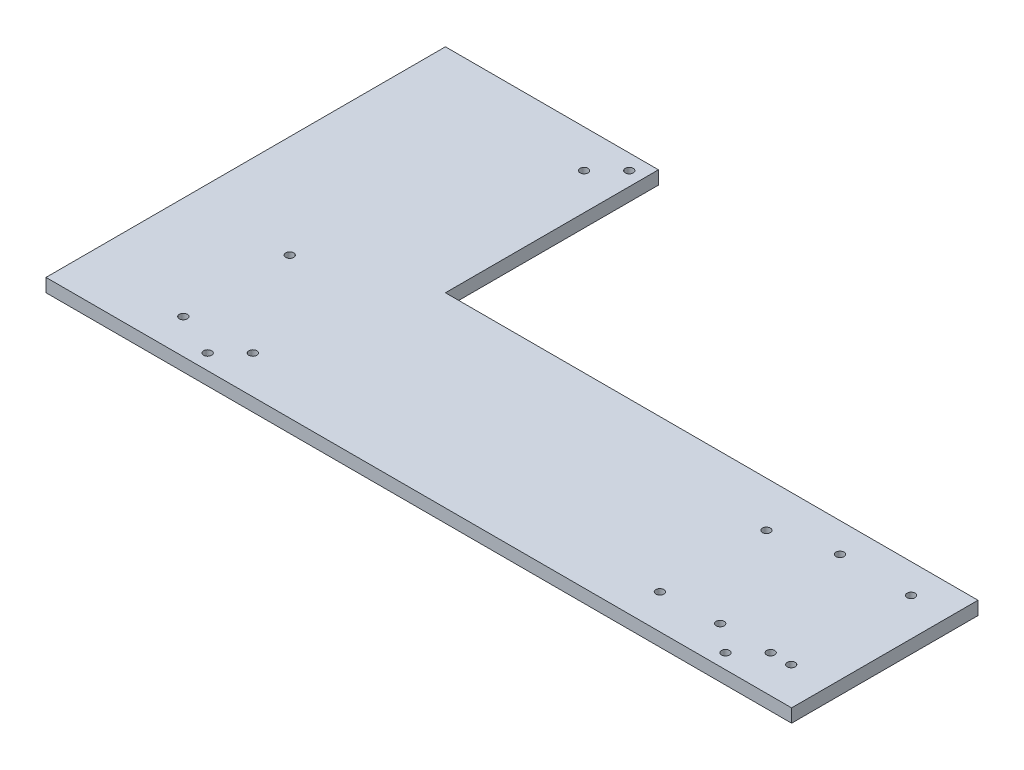
SolidWorks part; units mm, degrees
ref_plane "Front Plane" through (0, 0, 0) normal (0, 0, 1) x (1, 0, 0)
ref_plane "Top Plane" through (0, 0, 0) normal (0, 1, 0) x (1, 0, 0)
ref_plane "Right Plane" through (0, 0, 0) normal (1, 0, 0) x (0, 0, -1)
sketch "Sketch1" plane through (0, 0, 0) normal (0, 1, 0) x (1, 0, 0)
  line L1 (-124.5552, -60.7829) -> (155.4448, -60.7829)
  line L2 (-124.5552, -60.7829) -> (-124.5552, 9.2171)
  line L3 (-124.5552, 9.2171) -> (155.4448, 9.2171)
  line L4 (155.4448, -60.7829) -> (155.4448, 9.2171)
  line L6 (-124.5552, 9.2171) -> (-124.5552, 89.2171)
  line L7 (-124.5552, 89.2171) -> (-44.5552, 89.2171)
  line L8 (-44.5552, 9.2171) -> (-44.5552, 89.2171)
  circle A0 centre (141.3001, -46.7829) radius 1.5
  circle A1 centre (141.3001, -1.7829) radius 1.5
  circle A2 centre (114.6202, -1.7829) radius 1.5
  circle A3 centre (114.6202, -46.7829) radius 1.5
  circle A4 centre (92.978, -47.7829) radius 1.5
  circle A5 centre (92.978, -7.7829) radius 1.5
  circle A6 centre (-86.022, -47.7384) radius 1.5
  circle A7 centre (-86.022, -7.7829) radius 1.5
  circle A8 centre (-61.1247, -46.5403) radius 1.5
  circle A9 centre (-69.61, -55.0256) radius 1.5
  circle A10 centre (125.0964, -55.2612) radius 1.5
  circle A11 centre (133.5816, -46.7759) radius 1.5
  circle A12 centre (-49.7523, 83.4597) radius 1.5
  circle A13 centre (-58.2375, 74.9744) radius 1.5
  dimension "D5" = 3
  dimension "D6" = 3
  dimension "D7" = 3
  dimension "D8" = 3
  dimension "D9" = 3
  dimension "D10" = 3
  dimension "D11" = 3
  dimension "D12" = 3
  dimension "D13" = 3
  dimension "D14" = 3
  dimension "D1" = 280
  dimension "D2" = 70
  dimension "D3" = 80
  dimension "D4" = 150
extrude "Boss-Extrude1" add sketch "Sketch1" along normal blind 5 contours L1 L4 L3 L2 | L3 L8 L7 L6 region at (15.2752, 0, 25.7458) region at (-84.6228, 0, -49.1507)
